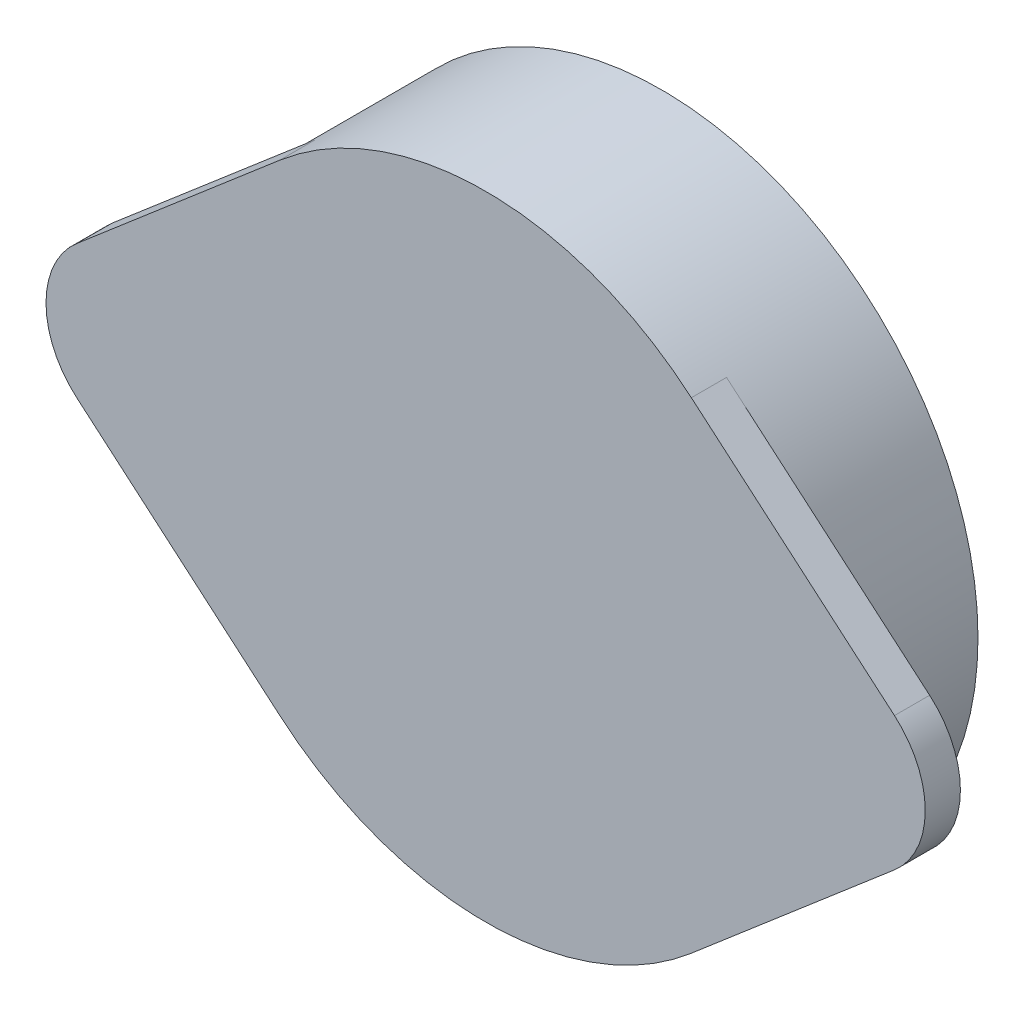
SolidWorks part; units mm, degrees
material "ABS"
ref_plane "Front Plane" through (0, 0, 0) normal (1, 0, 0) x (0, 1, 0)
ref_plane "Top Plane" through (0, 0, 0) normal (0, 0, 1) x (0, 1, 0)
ref_plane "Right Plane" through (0, 0, 0) normal (0, 1, 0) x (-1, 0, 0)
sketch "Sketch1" plane through (0, 0, 0) normal (0, 0, 1) x (0, 1, 0)
  line L0 (-28.5609, 0) -> (37.6947, 0) construction
  line L1 (-3.7997, 23.25) -> (-13.6788, 11.7)
  line L2 (3.7997, 23.25) -> (13.6788, 11.7)
  line L3 (3.7997, -23.25) -> (13.6788, -11.7)
  line L4 (-3.7997, -23.25) -> (-13.6788, -11.7)
  arc A0 (-13.6788, 11.7) -> (-13.6788, -11.7) centre (0, 0) ccw
  circle A1 centre (0, 0) radius 16
  arc A2 (3.7997, 23.25) -> (-3.7997, 23.25) centre (0, 20) ccw
  arc A3 (3.7997, -23.25) -> (-3.7997, -23.25) centre (0, -20) cw
  arc A4 (13.6788, -11.7) -> (13.6788, 11.7) centre (0, 0) ccw
  circle A5 centre (0, 0) radius 18
  dimension "D1" = 36
  dimension "D2" = 32
  dimension "D3" = 10
  dimension "D4" = 40
extrude "Boss-Extrude1" add sketch "Sketch1" against normal blind 2 contours A5 L4 A3 L3 | A5 L2 A2 L1 region at (-19.9307, 0, 0) region at (19.9307, 0, 0)
extrude "Boss-Extrude2" add sketch "Sketch1<3>" against normal blind 10 contours A0 L0 A1 A5 | L0 A5 A4 A1 region at (-16.4025, 0, 0) region at (0.4025, 17, 0)
sketch "Sketch1<3>" plane through (0, 0, 0) normal (0, 0, 1) x (0, 1, 0) same geometry as "Sketch1"
extrude "Boss-Extrude3" add sketch "Sketch1<4>" against normal blind 2 contours A1
sketch "Sketch1<4>" plane through (0, 0, 0) normal (0, 0, 1) x (0, 1, 0) same geometry as "Sketch1"
